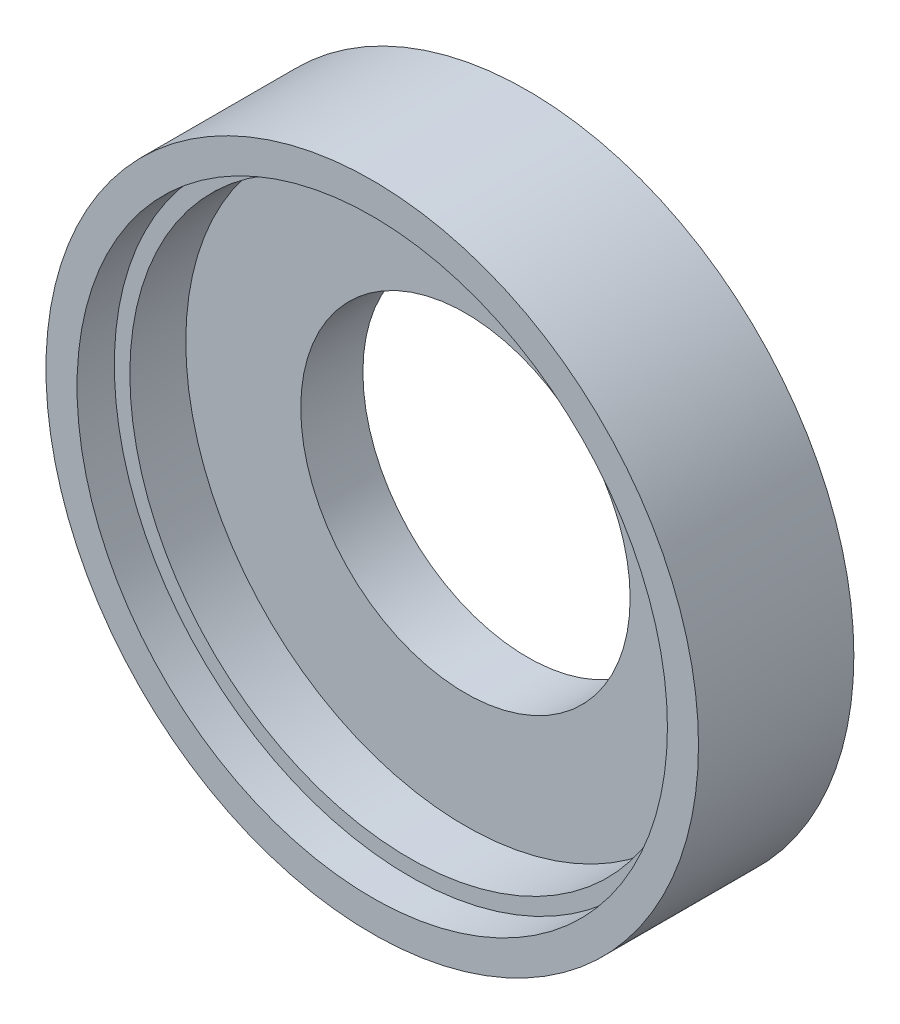
SolidWorks part; units mm, degrees
ref_plane "Front Plane" through (0, 0, 0) normal (0, 0, 1) x (1, 0, 0)
ref_plane "Top Plane" through (0, 0, 0) normal (0, 1, 0) x (1, 0, 0)
ref_plane "Right Plane" through (0, 0, 0) normal (1, 0, 0) x (0, 0, -1)
sketch "Sketch2" plane through (0, 0, 0) normal (0, 0, 1) x (1, 0, 0)
  circle A0 centre (0, 0) radius 45
  circle A1 centre (0, 0) radius 26.5
  circle A2 centre (0, 0) radius 47.5
  circle A3 centre (0, 0) radius 52.5
  dimension "D1" = 105
  dimension "D2" = 95
  dimension "D3" = 90
  dimension "D4" = 53
extrude "Boss-Extrude1" add sketch "Sketch2" along normal blind 25 contours A3 A2 region at (-51.0151, 0, 0)
extrude "Boss-Extrude5" add sketch "Sketch2<6>" along normal blind 19 contours A2 A0 region at (-46.1565, 0, 0)
sketch "Sketch2<6>" plane through (0, 0, 0) normal (0, 0, 1) x (1, 0, 0) same geometry as "Sketch2"
extrude "Boss-Extrude6" add sketch "Sketch2<7>" along normal blind 10 contours A0 A1 region at (-43.7272, 0, 0)
sketch "Sketch2<7>" plane through (0, 0, 0) normal (0, 0, 1) x (1, 0, 0) same geometry as "Sketch2"
